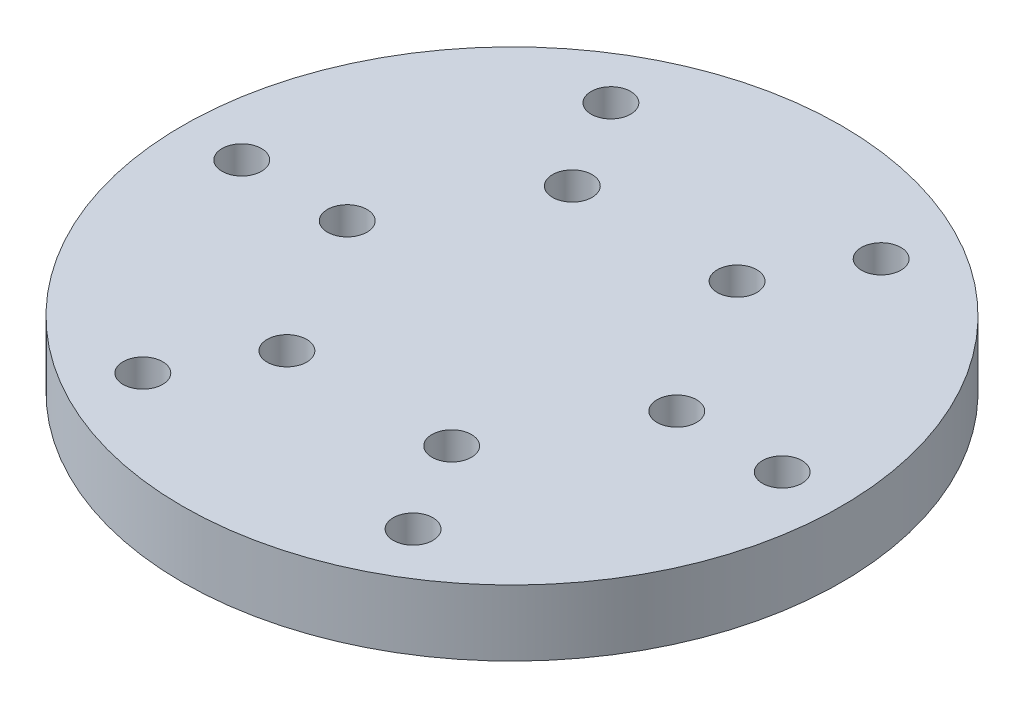
SolidWorks part; units mm, degrees
ref_plane "Front Plane" through (0, 0, 0) normal (0, 0, 1) x (1, 0, 0)
ref_plane "Top Plane" through (0, 0, 0) normal (0, 1, 0) x (1, 0, 0)
ref_plane "Right Plane" through (0, 0, 0) normal (1, 0, 0) x (0, 0, -1)
sketch "Sketch1" plane through (0, 0, 0) normal (0, 1, 0) x (1, 0, 0)
  line L0 (0, 0) -> (25, 0) construction
  line L1 (25, 0) -> (33, 0) construction
  circle A0 centre (0, 0) radius 1.5 construction
  circle A2 centre (25, 0) radius 1.5
  circle A3 centre (33, 0) radius 1.5
  circle A6 centre (12.5, 0) radius 25
  circle A7 centre (12.5, 0) radius 12.5 construction
  circle A8 centre (18.75, -10.8253) radius 1.5
  circle A9 centre (6.25, -10.8253) radius 1.5
  circle A10 centre (0, 0) radius 1.5
  circle A11 centre (6.25, 10.8253) radius 1.5
  circle A12 centre (18.75, 10.8253) radius 1.5
  circle A13 centre (12.5, 0) radius 20.5 construction
  circle A14 centre (22.75, -17.7535) radius 1.5
  circle A15 centre (2.25, -17.7535) radius 1.5
  circle A16 centre (-8, 0) radius 1.5
  circle A17 centre (2.25, 17.7535) radius 1.5
  circle A18 centre (22.75, 17.7535) radius 1.5
  point P23 (12.5, 0)
  point P34 (12.5, 0)
  dimension "D2" = 3
  dimension "D3" = 3
  dimension "D4" = 3
  dimension "D5" = 50
  dimension "D6" = 6
  dimension "D9" = 41
  dimension "D1" = 25
  dimension "D7" = 8
  dimension "D8" = 6
extrude "Boss-Extrude1" add sketch "Sketch1" along normal blind 5 contours A0 | A6 A2 | A6 A3 region at (12.5, 0, 0)
